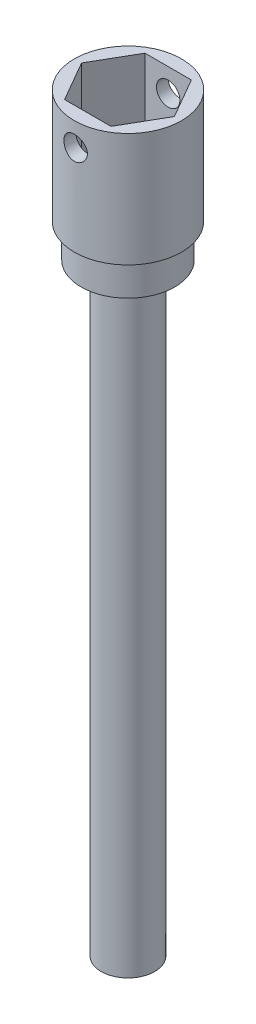
SolidWorks part; units mm, degrees
ref_plane "Front Plane" through (0, 0, 0) normal (0, 0, 1) x (1, 0, 0)
ref_plane "Top Plane" through (0, 0, 0) normal (0, 1, 0) x (1, 0, 0)
ref_plane "Right Plane" through (0, 0, 0) normal (1, 0, 0) x (0, 0, -1)
sketch "Sketch1" plane through (0, 0, 0) normal (0, 1, 0) x (-1, 0, 0)
  line L1 (6.9282, 0) -> (3.4641, 6)
  line L2 (3.4641, 6) -> (-3.4641, 6)
  line L3 (-3.4641, 6) -> (-6.9282, 0)
  line L4 (-6.9282, 0) -> (-3.4641, -6)
  line L5 (-3.4641, -6) -> (3.4641, -6)
  line L6 (3.4641, -6) -> (6.9282, 0)
  circle A0 centre (0, 0) radius 8
  circle A1 centre (0, 0) radius 6 construction
  point P3 (0, 0)
  point P11 (0, 0)
  dimension "D1" = 16
  dimension "D2" = 6.9282
  dimension "D3" = 6
extrude "Boss-Extrude1" add sketch "Sketch1" along normal blind 17
sketch "Sketch2" plane through (0, 0, -6) normal (0, 0, 1) x (1, 0, 0)
  line L0 (0, 0) -> (0, 11.75) construction
  circle A0 centre (0, 13.5) radius 1.75
  point P2 (0, 0)
  dimension "D1" = 3.5
  dimension "D3" = 8
  dimension "D2" = 13.5
extrude "Cut-Extrude2" cut sketch "Sketch2" against normal through all and the other way through all contours A0
sketch "Sketch3" plane through (0, 0, 0) normal (0, -1, 0) x (1, 0, 0)
  circle A0 centre (0, 0) radius 4
  dimension "D1" = 8
extrude "Boss-Extrude2" add sketch "Sketch3" along normal blind 95
sketch "Sketch5" plane through (0, 0, 0) normal (0, -1, 0) x (1, 0, 0)
  circle A0 centre (0, 0) radius 4.005
  circle A2 centre (0, 0) radius 7
  dimension "D1" = 8.01
  dimension "D2" = 14
extrude "Boss-Extrude8" add sketch "Sketch5" along normal blind 5
